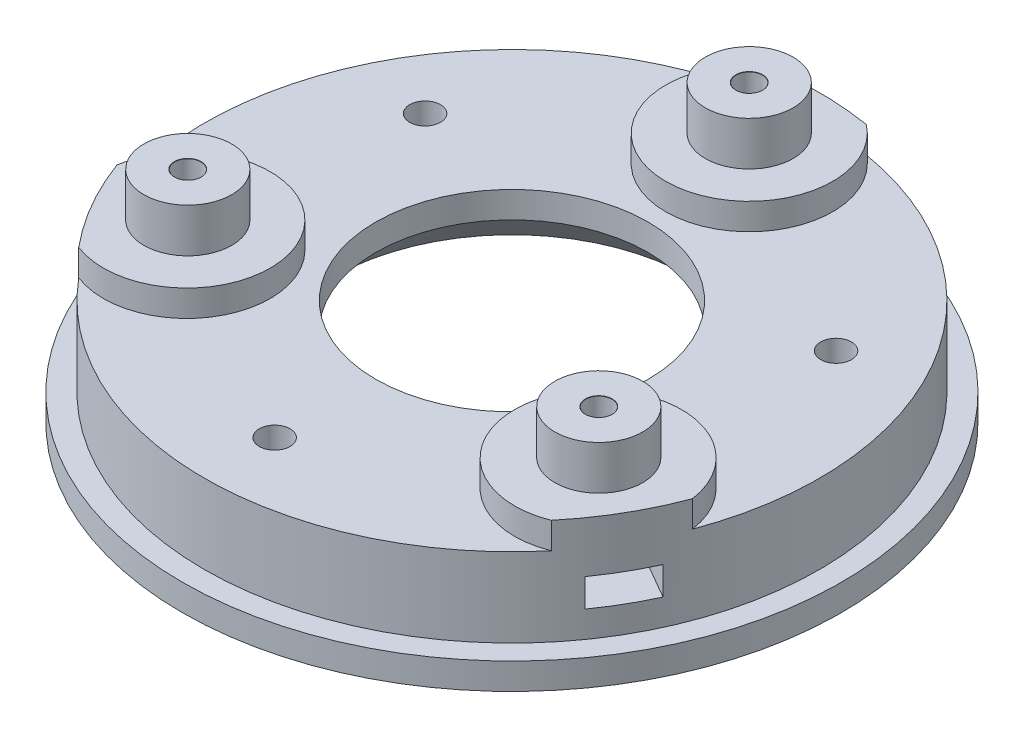
SolidWorks part; units mm, degrees
note: The reader was unsure of these and kept them because the rebuilt part matched: shared geometry of "Sketch1<3>".
ref_plane "Front Plane" through (0, 0, 0) normal (0, 0, 1) x (1, 0, 0)
ref_plane "Top Plane" through (0, 0, 0) normal (0, 1, 0) x (1, 0, 0)
ref_plane "Right Plane" through (0, 0, 0) normal (1, 0, 0) x (0, 0, -1)
sketch "Sketch1" plane through (0, 0, 0) normal (0, 1, 0) x (1, 0, 0)
  circle A0 centre (0, 0) radius 37.5
  circle A1 centre (0, 0) radius 35
  circle A2 centre (0, 0) radius 14.5
  dimension "D1" = 75
  dimension "D2" = 70
  dimension "D3" = 29
extrude "Boss-Extrude1" add sketch "Sketch1" along normal blind 3 contours A0
extrude "Boss-Extrude2" add sketch "Sketch1<3>" along normal blind 12 contours A1
sketch "Sketch1<3>" plane through (0, 0, 0) normal (0, 1, 0) x (1, 0, 0) same geometry as "Sketch1"
sketch "Sketch4" plane through (0, 12, 0) normal (0, 1, 0) x (1, 0, 0)
  circle A0 centre (0, 0) radius 15.5
  dimension "D1" = 31
extrude "Cut-Extrude1" cut sketch "Sketch4" against normal blind 15
sketch "Sketch5" plane through (0, 12, 0) normal (0, 1, 0) x (1, 0, 0)
  circle A4 centre (0, 0) radius 27 construction
  circle A5 centre (0, 0) radius 27 construction
  arc A6 (-5.813, 34.5139) -> (5.813, 34.5139) centre (0, 27) ccw
  arc A7 (32.7885, -12.244) -> (26.8852, -22.4095) centre (23.3827, -13.5787) ccw
  arc A8 (-26.9008, -22.3908) -> (-32.8414, -12.1014) centre (-23.4509, -13.5394) ccw
  circle A9 centre (0, 0) radius 35
  point P13 (-0.0227, -0.0394)
  circle M5 centre (0, 0) radius 35
  dimension "D1" = 54
  dimension "D2" = 54
  dimension "D3" = 19
  dimension "D4" = 70
extrude "Boss-Extrude3" add sketch "Sketch5" along normal blind 3 contours A6 M5 | A8 M5 | A7 M5
sketch "Sketch18" plane through (0, 15, 0) normal (0, 1, 0) x (1, 0, 0)
  line L0 (0, 30.8938) -> (0, -33.1494) construction
  circle A0 centre (0, 0) radius 27 construction
  circle A1 centre (0, 27) radius 5
  circle A2 centre (23.3827, -13.5) radius 5
  circle A3 centre (-23.3827, -13.5) radius 5
  point P13 (0, 0)
  dimension "D1" = 54
  dimension "D2" = 10
extrude "Boss-Extrude4" add sketch "Sketch18" along normal blind 5
sketch "Sketch22" plane through (0, 20, 0) normal (0, 1, 0) x (1, 0, 0)
  circle A0 centre (-23.3827, -13.5) radius 2.5
  dimension "D1" = 5
chamfer "Chamfer1" distance 9 angle 45 1 edges at (0, 0, 15.5)
hole_wizard "Ø3.0mm Dowel Hole1" positions "Sketch25" profile "Sketch26" hole size "Ø3.0" standard "ANSI Metric" end condition through all
sketch "Sketch25" plane through (0, 20, 0) normal (0, 1, 0) x (1, 0, 0)
  point P0 (0, 27)
  point P3 (-23.3827, -13.5)
  point P6 (23.3827, -13.5)
sketch "Sketch26" plane through (0, 20, -27) normal (1, 0, 0) x (0, 0, 1)
  line L0 (0, 0) -> (0, 20)
  line L1 (0, 20) -> (1.5, 20)
  line L2 (1.5, 20) -> (1.5, 0.025)
  line L3 (1.5, 0.025) -> (1.525, 0)
  line L5 (1.525, 0) -> (0, 0)
  line L6 (-1.5, 0.025) -> (-1.525, 0) construction
  line L11 (0, -6.35) -> (0, 107.95) construction
  dimension "Thru Hole Dia." = 3
  dimension "Thru Hole Depth" = 20
  dimension "Near C'Sink Dia." = 3.05
  dimension "Near C'Sink Angle" = 90
sketch "Sketch27" plane through (0, 12, 0) normal (0, 1, 0) x (1, 0, 0)
  line L0 (0, 0) -> (23.3827, -13.5) construction
  line L1 (0, 0) -> (24.8941, 14.3726) construction
  line L2 (0, 0) -> (0, 27) construction
  circle A0 centre (0, 0) radius 27 construction
  circle A1 centre (23.3827, 13.5) radius 1.75
  circle A2 centre (0, -27) radius 1.75
  circle A3 centre (-23.3827, 13.5) radius 1.75
  circle A4 centre (23.3827, -13.5) radius 1.525 construction
  point P15 (0, 0)
  dimension "D1" = 54
  dimension "D3" = 3.5
  dimension "D2" = 60
  dimension "D4" = 3
extrude "Cut-Extrude2" cut sketch "Sketch27" against normal through all
sketch "Sketch28" plane through (0, 0, 0) normal (0, -1, 0) x (1, 0, 0)
  line L0 (0, -30.7528) -> (0, 0) construction
  line L1 (3.25, -25.1236) -> (0, -23.2472)
  line L2 (0, -23.2472) -> (-3.25, -25.1236)
  line L3 (-3.25, -25.1236) -> (-3.25, -28.8764)
  line L4 (-3.25, -28.8764) -> (0, -30.7528)
  line L5 (0, -30.7528) -> (3.25, -28.8764)
  line L6 (3.25, -28.8764) -> (3.25, -25.1236)
  line L7 (-3.25, -28.8764) -> (-3.25, -37.3589)
  line L8 (3.25, -28.8764) -> (3.25, -37.3589)
  circle A0 centre (0, -27) radius 3.25 construction
  circle A1 centre (0, 0) radius 37.5 construction
  circle A2 centre (0, 0) radius 37.5
  circle A3 centre (0, -27) radius 1.525 construction
  dimension "D1" = 6.5
extrude "Cut-Extrude3" cut sketch "Sketch28" against normal blind 3.2 from offset 6 offset against normal yes
pattern_circular "CirPattern1" count 3 over 360 about axis through (0, 0, 0) along (0, 1, 0) of "Cut-Extrude3"
sketch "Sketch29" plane through (0, 0, 0) normal (0, -1, 0) x (1, 0, 0)
  circle A0 centre (0, 0) radius 32.5
  dimension "D1" = 65
extrude "Cut-Extrude4" cut sketch "Sketch29" against normal blind 4
chamfer "Chamfer2" distance 2 angle 45 1 edges at (0, 4, -32.5)
